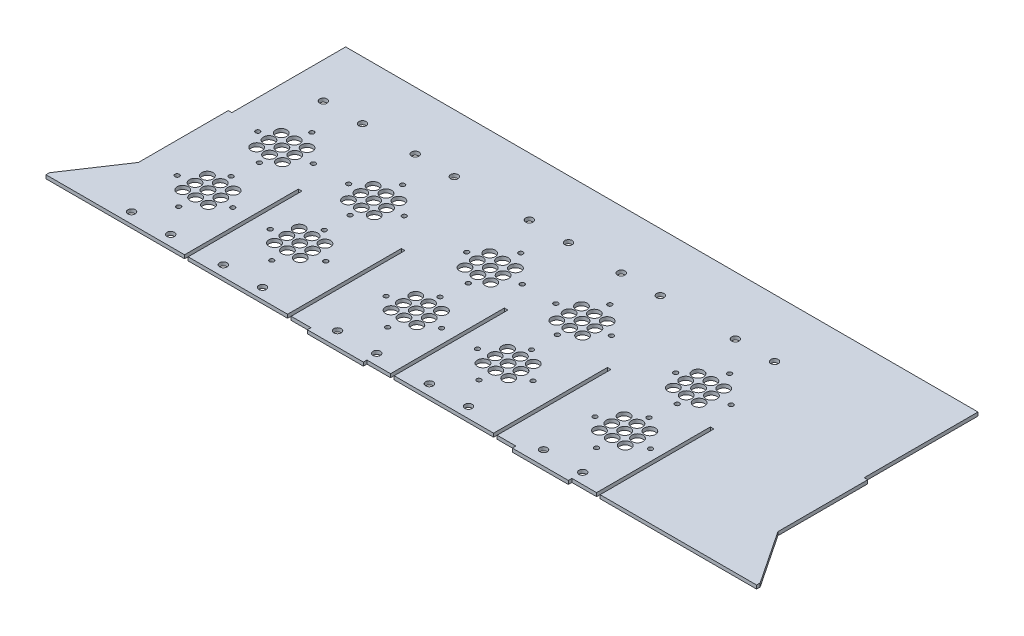
SolidWorks part; units mm, degrees
material "6061-T6 (SS)"
ref_plane "X-Y Datum" through (0, 0, 0) normal (0, 0, 1) x (1, 0, 0)
ref_plane "X-Z Datum" through (0, 0, 0) normal (0, 1, 0) x (1, 0, 0)
ref_plane "Y-Z Datum" through (0, 0, 0) normal (1, 0, 0) x (0, 0, -1)
sketch "Sketch1" plane through (0, 0, 0) normal (0, 0, 1) x (1, 0, 0)
  line L1 (-285.4305, -1.5875) -> (285.4305, -1.5875)
  line L2 (-285.4305, -1.5875) -> (-285.4305, 1.5875)
  line L3 (-285.4305, 1.5875) -> (285.4305, 1.5875)
  line L4 (285.4305, -1.5875) -> (285.4305, 1.5875)
  line L5 (-285.4305, -1.5875) -> (285.4305, 1.5875) construction
  line L6 (-285.4305, 1.5875) -> (285.4305, -1.5875) construction
  point P0 (0, 0)
  dimension "D1" = 570.861
  dimension "D2" = 3.175
extrude "Boss-Extrude1" add sketch "Sketch1" along normal blind 232.6
sketch "Sketch2" plane through (0, 1.5875, 0) normal (0, 1, 0) x (1, 0, 0)
  line L0 (-176.5505, -181.8) -> (-285.4305, -181.8) construction
  line L1 (-285.4305, -232.6) -> (-285.4305, 0) construction
  line L3 (285.4305, -232.6) -> (-285.4305, -232.6) construction
  line L4 (-178.0615, -232.6) -> (-174.8865, -232.6)
  line L6 (-178.0615, -118.3) -> (-174.8865, -118.3)
  line L8 (-178.0615, -232.6) -> (-174.8865, -232.6)
  line L9 (-178.0615, -232.6) -> (-178.0615, -118.3)
  line L10 (-178.0615, -118.3) -> (-174.8865, -118.3)
  line L11 (-174.8865, -232.6) -> (-174.8865, -118.3)
  line L17 (-178.0615, -118.3) -> (-174.8865, -118.3)
  line L38 (-285.4305, 0) -> (-282.2555, 0)
  line L39 (-285.4305, 0) -> (-285.4305, -101.6)
  line L40 (-285.4305, -101.6) -> (-282.2555, -101.6)
  line L41 (-282.2555, 0) -> (-282.2555, -101.6)
  line L42 (285.4305, 0) -> (282.2555, 0)
  line L43 (285.4305, 0) -> (285.4305, -101.6)
  line L44 (285.4305, -101.6) -> (282.2555, -101.6)
  line L45 (282.2555, 0) -> (282.2555, -101.6)
  line M3 (285.4305, 0) -> (-285.4305, 0)
  line M4 (-285.4305, 0) -> (-285.4305, -232.6)
  line M6 (285.4305, -232.6) -> (285.4305, 0)
  dimension "D2" = 50.8
  dimension "D3" = 3.175
  dimension "D6" = 3.175
  dimension "D7" = 101.6
  dimension "D4" = 114.3
  dimension "D8" = 3.175
  dimension "D9" = 101.6
sketch "Sketch6" plane through (0, 0, 232.6) normal (0, 0, 1) x (1, 0, 0)
  line L0 (285.4305, 1.5875) -> (-285.4305, 1.5875) construction
  line L1 (-285.4305, 1.5875) -> (-285.4305, -1.5875) construction
  line L14 (152.263, -1.5875) -> (152.263, 1.5875)
  line L15 (102.263, 1.5875) -> (152.263, 1.5875)
  line L16 (102.263, -1.5875) -> (152.263, 1.5875) construction
  line L17 (102.263, 1.5875) -> (152.263, -1.5875) construction
  line L18 (102.263, -1.5875) -> (152.263, -1.5875)
  line L19 (102.263, -1.5875) -> (102.263, 1.5875)
  line L20 (-30.6951, -1.5875) -> (-30.6951, 1.5875)
  line L21 (-80.6951, 1.5875) -> (-30.6951, 1.5875)
  line L22 (-80.6951, -1.5875) -> (-30.6951, 1.5875) construction
  line L23 (-80.6951, 1.5875) -> (-30.6951, -1.5875) construction
  line L24 (-80.6951, -1.5875) -> (-30.6951, -1.5875)
  line L25 (-80.6951, -1.5875) -> (-80.6951, 1.5875)
  point P4 (-55.6951, 0)
  point P5 (127.263, 0)
  dimension "D1" = 3.175
  dimension "D2" = 50
  dimension "D3" = 3.175
  dimension "D4" = 229.7354
  dimension "D5" = 182.9581
sketch "Sketch7" plane through (0, -1.5875, 0) normal (0, -1, 0) x (-1, 0, 0)
  line L1 (-285.4305, -232.6) -> (-285.4305, 0) construction
  circle A2 centre (-245.6805, -11.2916) radius 3.302
  dimension "D1" = 39.75
  dimension "D2" = 6.604
extrude "Cut-Extrude4" [suppressed] cut sketch "Sketch7" against normal through all contours A2
extrude "Boss-Extrude2" add sketch "Sketch6" along normal blind 3.175
pattern_linear "LPattern1" [suppressed] count 6 spacing 93.98 of bodies 119
extrude "Cut-Extrude5" cut sketch "Sketch2" against normal through all contours L41 L40 M3 M4 | L45 L44 M3 M6 region at (283.843, 1.5875, 50.8) region at (-283.843, 1.5875, 50.8)
sketch "Sketch12" plane through (0, 1.5875, 0) normal (0, 1, 0) x (1, 0, 0)
  line L0 (-285.4305, -232.6) -> (-285.4305, -101.6) construction
  line L1 (-285.4305, -232.6) -> (-285.4305, -181.8)
  line L2 (285.4305, -232.6) -> (285.4305, -101.6) construction
  line L3 (285.4305, -232.6) -> (285.4305, -101.6)
  line L4 (-285.4305, -232.6) -> (-317.1805, -232.6)
  line L6 (-317.1805, -232.6) -> (-317.1805, -229.425)
  line L7 (-317.1805, -229.425) -> (-285.4305, -181.8)
  line M9 (-285.4305, -101.6) -> (-285.4305, -232.6)
  dimension "D1" = 31.75
  dimension "D2" = 50.8
  dimension "D3" = 3.175
extrude "Boss-Extrude3" add sketch "Sketch12" against normal blind 3.175 contours L4 M9 region at (-296.6364, 1.5875, 215.6044)
mirror "Mirror1" about plane through (0, 0, 0) normal (1, 0, 0) of "Boss-Extrude3"
sketch "Sketch13" plane through (0, -1.5875, 0) normal (0, -1, 0) x (1, 0, 0)
  line L0 (-193.4755, 232.6) -> (-193.4755, 131)
  line L1 (-317.1805, 232.6) -> (-80.6951, 232.6) construction
  line L2 (-282.2555, 0) -> (-282.2555, 101.6) construction
  line L3 (-193.4755, 232.6) -> (-190.3005, 232.6)
  line L5 (-193.4755, 232.6) -> (-193.4755, 131)
  line L6 (-193.4755, 131) -> (-190.3005, 131)
  line L7 (-190.3005, 232.6) -> (-190.3005, 131)
  line M23 (-80.6951, 232.6) -> (-317.1805, 232.6)
  dimension "D1" = 88.78
  dimension "D2" = 101.6
  dimension "D3" = 3.175
extrude "Cut-Extrude6" cut sketch "Sketch13" against normal through all contours L7 L0 L6 M23 region at (-191.888, -1.5875, 181.8)
pattern_linear "LPattern2" count 5 spacing 91.955 along (1, 0, 0) of "Cut-Extrude6"
sketch "Sketch14" plane through (0, 1.5875, 0) normal (0, 1, 0) x (1, 0, 0)
  circle A0 centre (-215.403, -51.825) radius 3 construction
  circle A1 centre (-250.328, -51.825) radius 3 construction
  circle A2 centre (-215.403, -223.075) radius 3 construction
  circle A3 centre (-250.328, -223.075) radius 3 construction
  circle A4 centre (-215.403, -51.825) radius 3 construction
  circle A5 centre (-250.328, -51.825) radius 3 construction
  circle A6 centre (-215.403, -223.075) radius 3 construction
  circle A7 centre (-250.328, -223.075) radius 3 construction
  circle A8 centre (-133.4455, -51.825) radius 3.3 construction
  circle A9 centre (-168.3705, -51.825) radius 3.3 construction
  circle A10 centre (-133.4455, -223.075) radius 3.3 construction
  circle A11 centre (-168.3705, -223.075) radius 3.3 construction
  circle A12 centre (-133.4455, -51.825) radius 3.3 construction
  circle A13 centre (-168.3705, -51.825) radius 3.3 construction
  circle A14 centre (-133.4455, -223.075) radius 3.3 construction
  circle A15 centre (-168.3705, -223.075) radius 3.3 construction
hole_wizard "M6 Clearance Hole1" positions "Sketch15" profile "Sketch16" hole size "M6" standard "ANSI Metric" end condition through all
sketch "Sketch15" plane through (0, 1.5875, 0) normal (0, 1, 0) x (1, 0, 0)
  point P0 (-250.328, -223.075)
  point P3 (-215.403, -223.075)
  point P6 (-215.403, -51.825)
  point P9 (-250.328, -51.825)
sketch "Sketch16" plane through (-250.328, 1.5875, 223.075) normal (1, 0, 0) x (0, 0, 1)
  line L0 (0, 0) -> (0, 3.175)
  line L1 (0, 3.175) -> (3.3, 3.175)
  line L2 (3.3, 3.175) -> (3.3, 0)
  line L5 (3.3, 0) -> (0, 0)
  line L11 (0, -6.35) -> (0, 107.95) construction
  dimension "Thru Hole Dia." = 6.6
  dimension "Thru Hole Depth" = 3.175
hole_wizard "M6 Clearance Hole2" positions "Sketch17" profile "Sketch18" hole size "M6" standard "ANSI Metric" end condition through all
sketch "Sketch17" plane through (0, 1.5875, 0) normal (0, 1, 0) x (1, 0, 0)
  point P0 (-168.3705, -223.075)
  point P3 (-133.4455, -223.075)
  point P6 (-168.3705, -51.825)
  point P9 (-133.4455, -51.825)
sketch "Sketch18" plane through (-168.3705, 1.5875, 223.075) normal (1, 0, 0) x (0, 0, 1)
  line L0 (0, 0) -> (0, 3.175)
  line L1 (0, 3.175) -> (3.3, 3.175)
  line L2 (3.3, 3.175) -> (3.3, 0)
  line L5 (3.3, 0) -> (0, 0)
  line L11 (0, -6.35) -> (0, 107.95) construction
  dimension "Thru Hole Dia." = 6.6
  dimension "Thru Hole Depth" = 3.175
pattern_linear "LPattern3" count 3 spacing 183.92 along (1, 0, 0) of "M6 Clearance Hole1"
pattern_linear "LPattern4" count 2 spacing 183.92 along (1, 0, 0) of "M6 Clearance Hole2"
sketch "Sketch20" plane through (0, 7.935, 0) normal (0, 1, 0) x (1, 0, 0)
  circle A0 centre (-206.4649, -104.6371) radius 2 construction
  circle A1 centre (-231.2504, -128.0582) radius 2 construction
  circle A2 centre (-256.0359, -104.6371) radius 2 construction
  circle A3 centre (-231.2504, -81.216) radius 2 construction
  circle A4 centre (-206.4649, -104.6371) radius 2
  circle A5 centre (-231.2504, -128.0582) radius 2
  circle A6 centre (-256.0359, -104.6371) radius 2
  circle A7 centre (-231.2504, -81.216) radius 2
  circle A8 centre (-174.9826, -174.6221) radius 2 construction
  circle A9 centre (-150.197, -198.0432) radius 2 construction
  circle A10 centre (-150.197, -151.201) radius 2 construction
  circle A11 centre (-125.4115, -174.6221) radius 2 construction
  circle A12 centre (-21.9991, -174.6221) radius 2 construction
  circle A13 centre (-46.7846, -198.0432) radius 2 construction
  circle A14 centre (-46.7846, -151.201) radius 2 construction
  circle A15 centre (-71.5702, -174.6221) radius 2 construction
  circle A16 centre (-174.9826, -174.6221) radius 2
  circle A17 centre (-150.197, -198.0432) radius 2
  circle A18 centre (-150.197, -151.201) radius 2
  circle A19 centre (-125.4115, -174.6221) radius 2
  circle A20 centre (-21.9991, -174.6221) radius 2
  circle A21 centre (-46.7846, -198.0432) radius 2
  circle A22 centre (-46.7846, -151.201) radius 2
  circle A23 centre (-71.5702, -174.6221) radius 2
  circle A24 centre (-125.4115, -104.6371) radius 2 construction
  circle A25 centre (-150.197, -128.0582) radius 2 construction
  circle A26 centre (-174.9826, -104.6371) radius 2 construction
  circle A27 centre (-150.197, -81.216) radius 2 construction
  circle A28 centre (-208.4991, -174.6221) radius 2 construction
  circle A29 centre (-233.2846, -198.0432) radius 2 construction
  circle A30 centre (-258.0702, -174.6221) radius 2 construction
  circle A31 centre (-233.2846, -151.201) radius 2 construction
  circle A32 centre (-125.4115, -104.6371) radius 2
  circle A33 centre (-150.197, -128.0582) radius 2
  circle A34 centre (-174.9826, -104.6371) radius 2
  circle A35 centre (-150.197, -81.216) radius 2
  circle A36 centre (-208.4991, -174.6221) radius 2
  circle A37 centre (-233.2846, -198.0432) radius 2
  circle A38 centre (-258.0702, -174.6221) radius 2
  circle A39 centre (-233.2846, -151.201) radius 2
  circle A40 centre (-44.7504, -128.0582) radius 2 construction
  circle A41 centre (-19.9649, -104.6371) radius 2 construction
  circle A42 centre (-44.7504, -81.216) radius 2 construction
  circle A43 centre (-69.5359, -104.6371) radius 2 construction
  circle A44 centre (-44.7504, -128.0582) radius 2
  circle A45 centre (-19.9649, -104.6371) radius 2
  circle A46 centre (-44.7504, -81.216) radius 2
  circle A47 centre (-69.5359, -104.6371) radius 2
  circle A48 centre (34.803, -198.0432) radius 2 construction
  circle A49 centre (59.5885, -174.6221) radius 2 construction
  circle A50 centre (34.803, -151.201) radius 2 construction
  circle A51 centre (10.0174, -174.6221) radius 2 construction
  circle A52 centre (34.803, -128.0582) radius 2 construction
  circle A53 centre (10.0174, -104.6371) radius 2 construction
  circle A54 centre (59.5885, -104.6371) radius 2 construction
  circle A55 centre (34.803, -81.216) radius 2 construction
  circle A56 centre (34.803, -198.0432) radius 2
  circle A57 centre (59.5885, -174.6221) radius 2
  circle A58 centre (34.803, -151.201) radius 2
  circle A59 centre (10.0174, -174.6221) radius 2
  circle A60 centre (34.803, -128.0582) radius 2
  circle A61 centre (10.0174, -104.6371) radius 2
  circle A62 centre (59.5885, -104.6371) radius 2
  circle A63 centre (34.803, -81.216) radius 2
  circle A64 centre (139.7154, -198.0432) radius 2 construction
  circle A65 centre (114.9298, -174.6221) radius 2 construction
  circle A66 centre (164.5009, -174.6221) radius 2 construction
  circle A67 centre (139.7154, -151.201) radius 2 construction
  circle A68 centre (166.5351, -104.6371) radius 2 construction
  circle A69 centre (141.7496, -128.0582) radius 2 construction
  circle A70 centre (116.9641, -104.6371) radius 2 construction
  circle A71 centre (141.7496, -81.216) radius 2 construction
  circle A72 centre (139.7154, -198.0432) radius 2
  circle A73 centre (114.9298, -174.6221) radius 2
  circle A74 centre (164.5009, -174.6221) radius 2
  circle A75 centre (139.7154, -151.201) radius 2
  circle A76 centre (166.5351, -104.6371) radius 2
  circle A77 centre (141.7496, -128.0582) radius 2
  circle A78 centre (116.9641, -104.6371) radius 2
  circle A79 centre (141.7496, -81.216) radius 2
extrude "Cut-Extrude8" cut sketch "Sketch20" against normal through all
sketch "Sketch21" plane through (0, 1.5875, 0) normal (0, 1, 0) x (1, 0, 0)
  circle A1 centre (-232.8655, -95.3433) radius 5 construction
  circle A2 centre (-244.3655, -95.3433) radius 5 construction
  circle A3 centre (-244.3655, -106.3433) radius 5 construction
  circle A4 centre (-244.3655, -117.3433) radius 5 construction
  circle A5 centre (-232.8655, -95.3433) radius 5
  circle A6 centre (-244.3655, -95.3433) radius 5
  circle A7 centre (-244.3655, -106.3433) radius 5
  circle A8 centre (-244.3655, -117.3433) radius 5
  circle A9 centre (-221.3655, -106.3433) radius 5 construction
  circle A10 centre (-232.8655, -106.3433) radius 5 construction
  circle A11 centre (-221.3655, -106.3433) radius 5
  circle A12 centre (-232.8655, -106.3433) radius 5
  circle A13 centre (-232.8655, -117.3433) radius 5 construction
  circle A14 centre (-221.3655, -117.3433) radius 5 construction
  circle A15 centre (-221.3655, -95.3433) radius 5 construction
  circle A16 centre (-232.8655, -117.3433) radius 5
  circle A17 centre (-221.3655, -117.3433) radius 5
  circle A18 centre (-221.3655, -95.3433) radius 5
  circle A37 centre (-244.3655, -183.3433) radius 5 construction
  circle A38 centre (-232.8655, -183.3433) radius 5 construction
  circle A39 centre (-221.3655, -183.3433) radius 5 construction
  circle A40 centre (-221.3655, -172.3433) radius 5 construction
  circle A41 centre (-221.3655, -161.3433) radius 5 construction
  circle A42 centre (-232.8655, -161.3433) radius 5 construction
  circle A43 centre (-232.8655, -172.3433) radius 5 construction
  circle A44 centre (-244.3655, -172.3433) radius 5 construction
  circle A45 centre (-244.3655, -161.3433) radius 5 construction
  circle A46 centre (-244.3655, -183.3433) radius 5
  circle A47 centre (-232.8655, -183.3433) radius 5
  circle A48 centre (-221.3655, -183.3433) radius 5
  circle A49 centre (-221.3655, -172.3433) radius 5
  circle A50 centre (-221.3655, -161.3433) radius 5
  circle A51 centre (-232.8655, -161.3433) radius 5
  circle A52 centre (-232.8655, -172.3433) radius 5
  circle A53 centre (-244.3655, -172.3433) radius 5
  circle A54 centre (-244.3655, -161.3433) radius 5
extrude "Cut-Extrude9" cut sketch "Sketch21" against normal through all
pattern_linear "LPattern5" count 3 spacing 186 along (1, 0, 0) of "Cut-Extrude9"
sketch "Sketch22" plane through (0, 1.5875, 0) normal (0, 1, 0) x (1, 0, 0)
  circle A0 centre (-139.408, -117.3433) radius 5 construction
  circle A1 centre (-150.908, -117.3433) radius 5 construction
  circle A2 centre (-162.408, -117.3433) radius 5 construction
  circle A3 centre (-162.408, -106.3433) radius 5 construction
  circle A4 centre (-150.908, -106.3433) radius 5 construction
  circle A5 centre (-139.408, -106.3433) radius 5 construction
  circle A6 centre (-139.408, -95.3433) radius 5 construction
  circle A7 centre (-150.908, -95.3433) radius 5 construction
  circle A8 centre (-162.408, -95.3433) radius 5 construction
  circle A9 centre (-139.408, -117.3433) radius 5
  circle A10 centre (-150.908, -117.3433) radius 5
  circle A11 centre (-162.408, -117.3433) radius 5
  circle A12 centre (-162.408, -106.3433) radius 5
  circle A13 centre (-150.908, -106.3433) radius 5
  circle A14 centre (-139.408, -106.3433) radius 5
  circle A15 centre (-139.408, -95.3433) radius 5
  circle A16 centre (-150.908, -95.3433) radius 5
  circle A17 centre (-162.408, -95.3433) radius 5
  circle A18 centre (-139.408, -183.3433) radius 5 construction
  circle A19 centre (-139.408, -172.3433) radius 5 construction
  circle A20 centre (-139.408, -161.3433) radius 5 construction
  circle A21 centre (-150.908, -161.3433) radius 5 construction
  circle A22 centre (-150.908, -172.3433) radius 5 construction
  circle A23 centre (-150.908, -183.3433) radius 5 construction
  circle A24 centre (-162.408, -183.3433) radius 5 construction
  circle A25 centre (-162.408, -172.3433) radius 5 construction
  circle A26 centre (-162.408, -161.3433) radius 5 construction
  circle A27 centre (-139.408, -183.3433) radius 5
  circle A28 centre (-139.408, -172.3433) radius 5
  circle A29 centre (-139.408, -161.3433) radius 5
  circle A30 centre (-150.908, -161.3433) radius 5
  circle A31 centre (-150.908, -172.3433) radius 5
  circle A32 centre (-150.908, -183.3433) radius 5
  circle A33 centre (-162.408, -183.3433) radius 5
  circle A34 centre (-162.408, -172.3433) radius 5
  circle A35 centre (-162.408, -161.3433) radius 5
extrude "Cut-Extrude10" cut sketch "Sketch22" against normal through all
pattern_linear "LPattern6" count 2 spacing 186 along (1, 0, 0) of "Cut-Extrude10"
